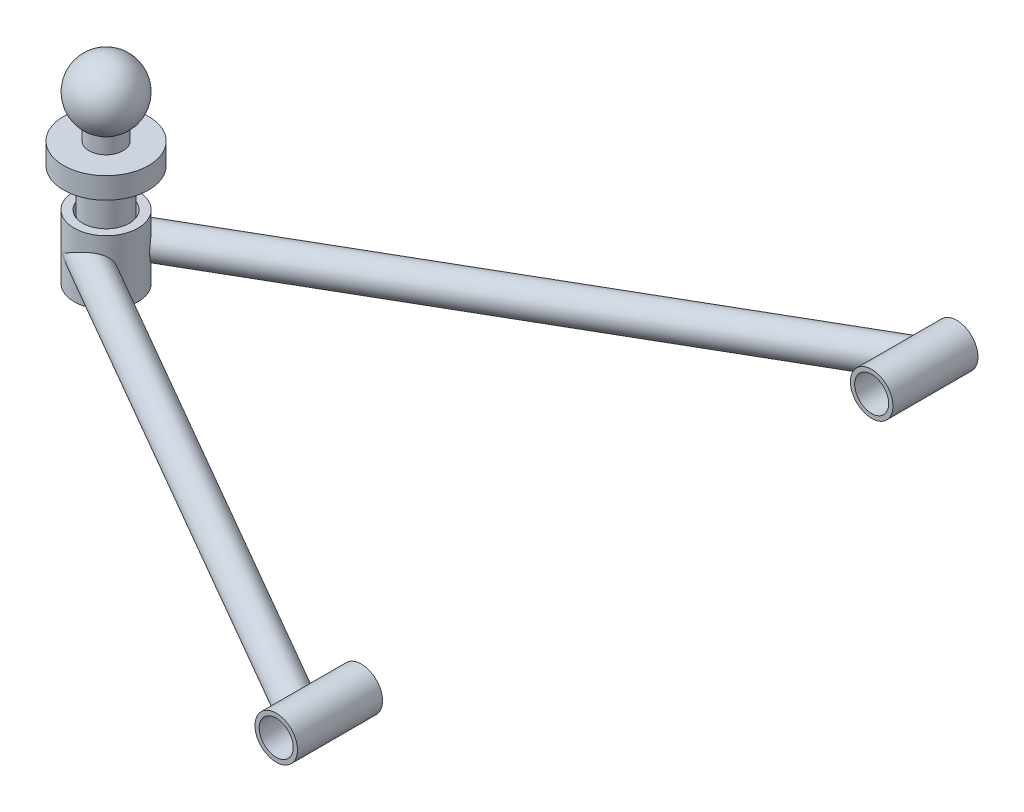
SolidWorks part; units mm, degrees
note: '?' marks a value the reader was unsure of.
ref_plane "前视基准面" through (0, 0, 0) normal (0, 0, 1) x (1, 0, 0)
ref_plane "上视基准面" through (0, 0, 0) normal (0, 1, 0) x (1, 0, 0)
ref_plane "右视基准面" through (0, 0, 0) normal (1, 0, 0) x (0, 0, -1)
sketch "草图1" plane through (0, 0, 0) normal (0, 1, 0) x (1, 0, 0)
  circle A0 centre (0, 0) radius 15
  circle A1 centre (0, 0) radius 11
  dimension "D2" = 30
  dimension "D1" = 4
extrude "凸台-拉伸1" add sketch "草图1" along normal mid plane 30
ref_axis "基准轴1" through (0, 71.5492, 0) along (0, -1, 0)?
ref_plane "基准面1" through (0, 0, 0) normal (0.866, 0, 0.5) x (0, -1, 0)
sketch "草图2" plane through (0, 0, 0) normal (0.866, 0, 0.5) x (0, -1, 0)
  line L0 (-15, -15) -> (15, -15) construction
  line L2 (0, 19.8599) -> (0, -24.4728) construction
  circle A0 centre (0, -7.5) radius 7.5
  circle A1 centre (0, -7.5) radius 5.5
  point P5 (0, -7.5)
  dimension "D1" = 15
  dimension "D2" = 2
sketch "草图3" plane through (0, 0, 0) normal (0, 0, 1) x (1, 0, 0)
  line L0 (0, 15) -> (0, -15) construction
  circle A0 centre (240, 0) radius 10
  circle A1 centre (240, 0) radius 8
  point P4 (238.8352, 0)
  dimension "D1" = 20
  dimension "D3" = 240
  dimension "D2" = 2
extrude "凸台-拉伸3" add sketch "草图3" along normal blind 40 from offset 120 separate body
extrude "凸台-拉伸4" add sketch "草图2" along normal up to next and the other way up to next from offset 50
mirror "镜向16" about plane through (0, 0, 0) normal (0, 0, 1) of bodies 110
sketch "草图4" plane through (0, 0, 0) normal (1, 0, 0) x (0, 0, -1)
  line L0 (0, 71.5492) -> (0, -15) construction
  line L1 (-8, 43) -> (-8, 50.3114)
  line L2 (-8, 43) -> (-20, 43)
  line L3 (15, 15) -> (-15, 15) construction
  line L4 (-10, 33) -> (-20, 33)
  line L5 (-20, 43) -> (-20, 33)
  line L7 (-10, 33) -> (-10, 13)
  line L8 (-10, 13) -> (0, 13)
  line L9 (0, 78) -> (0, 13)
  arc A0 (0, 78) -> (-8, 50.3114) centre (0, 63) ccw
  point P4 (0, 70.4294)
  dimension "D4" = 15
  dimension "D7" = 50
  dimension "D1" = 10
  dimension "D2" = 10
  dimension "D3" = 20
  dimension "D5" = 8
  dimension "D6" = 20
  dimension "D8" = 2
revolve "旋转1" add sketch "草图4" angle 360 about L9
